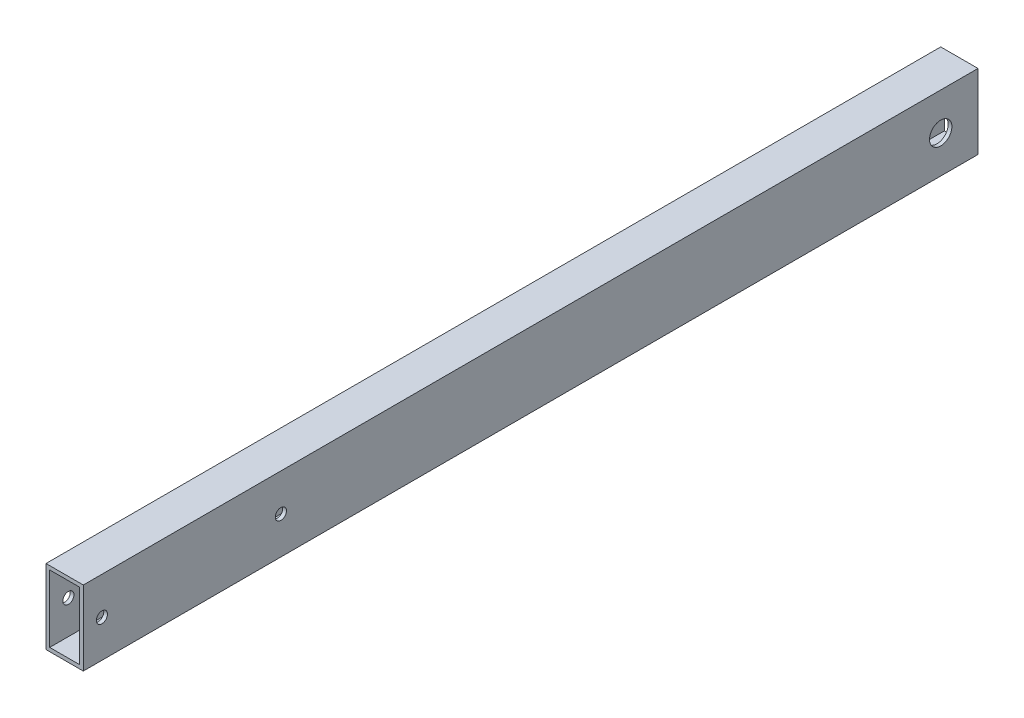
SolidWorks part; units mm, degrees
ref_plane "Front Plane" through (0, 0, 0) normal (0, 0, 1) x (1, 0, 0)
ref_plane "Top Plane" through (0, 0, 0) normal (0, 1, 0) x (1, 0, 0)
ref_plane "Right Plane" through (0, 0, 0) normal (1, 0, 0) x (0, 0, -1)
sketch "Sketch1" plane through (0, 0, 0) normal (0, 0, 1) x (1, 0, 0)
  line L0 (-4, 9) -> (4, 9)
  line L1 (-5, -10) -> (5, -10)
  line L2 (-5, -10) -> (-5, 10)
  line L3 (-5, 10) -> (5, 10)
  line L4 (5, -10) -> (5, 10)
  line L5 (-5, -10) -> (5, 10) construction
  line L6 (-5, 10) -> (5, -10) construction
  line L7 (4, -9) -> (4, 9)
  line L8 (-4, -9) -> (4, -9)
  line L9 (-4, -9) -> (-4, 9)
  point P0 (0, 0)
  dimension "D2" = 10
  dimension "D3" = 20
  dimension "D1" = 1
extrude "Boss-Extrude1" add sketch "Sketch1" along normal blind 240
sketch "Sketch2" plane through (5, 0, 0) normal (1, 0, 0) x (0, 0, -1)
  line L0 (-240, 0) -> (0, 0) construction
  line L1 (-240, -10) -> (-240, 10) construction
  line L2 (0, -10) -> (0, 10) construction
  circle A0 centre (-10, 0) radius 3
  circle A1 centre (-235, 0) radius 1.5
  circle A2 centre (-187, 0) radius 1.5
  dimension "D1" = 6
  dimension "D2" = 10
  dimension "D4" = 3
  dimension "D5" = 48
  dimension "D3" = 5
extrude "Cut-Extrude1" cut sketch "Sketch2" against normal through all
